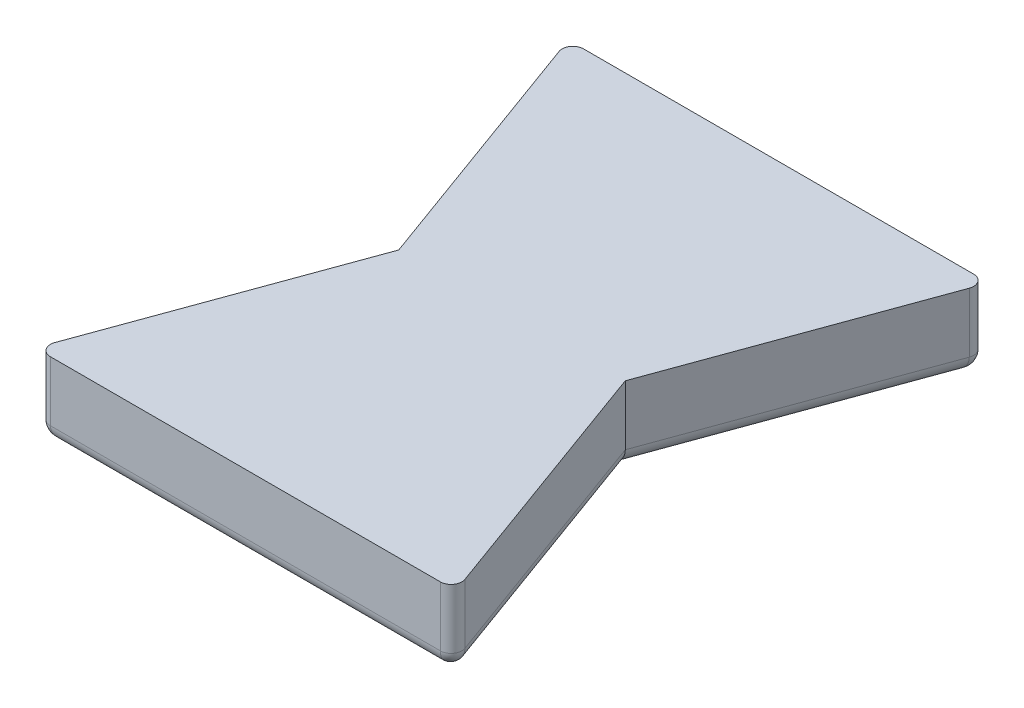
SolidWorks part; units mm, degrees
ref_plane "Front Plane" through (0, 0, 0) normal (0, 0, 1) x (1, 0, 0)
ref_plane "Top Plane" through (0, 0, 0) normal (0, 1, 0) x (1, 0, 0)
ref_plane "Right Plane" through (0, 0, 0) normal (1, 0, 0) x (0, 0, -1)
sketch "Sketch1" plane through (0, 0, 0) normal (0, 1, 0) x (1, 0, 0)
  line L0 (-13.0563, 17.5) -> (14.6826, 17.5) construction
  line L1 (14.6826, 17.5) -> (8.3132, 0) construction
  line L2 (8.3132, 0) -> (14.6826, -17.5) construction
  line L3 (14.6826, -17.5) -> (-13.0563, -17.5) construction
  line L4 (-13.0563, -17.5) -> (-6.6868, 0) construction
  line L5 (-6.6868, 0) -> (-13.0563, 17.5) construction
  line L6 (-6.6868, 0) -> (8.3132, 0) construction
  line L7 (14.5398, -17.4) -> (-12.9135, -17.4)
  line L8 (-12.9135, -17.4) -> (-6.5804, 0)
  line L9 (-6.5804, 0) -> (-12.9135, 17.4)
  line L10 (-12.9135, 17.4) -> (14.5398, 17.4)
  line L11 (14.5398, 17.4) -> (8.2067, 0)
  line L12 (8.2067, 0) -> (14.5398, -17.4)
  dimension "D1" = 15
  dimension "D2" = 35
  dimension "D3" = 70
  dimension "D4" = 0.1
extrude "Boss-Extrude1" add sketch "Sketch1" along normal blind 4.9
fillet "Fillet1" radius 0.7 4 edges at (14.5398, 2.45, -17.4) (-12.9135, 2.45, -17.4) (-12.9135, 2.45, 17.4) (14.5398, 2.45, 17.4)
fillet "Fillet2" radius 1 10 edges at (-12.4872, 0, -17.1015) (-9.576, 0, -8.2303) (-9.576, 0, 8.2303) (-12.4872, 0, 17.1015) (0.8132, 0, 17.4) (14.1135, 0, 17.1015) (11.2023, 0, 8.2303) (11.2023, 0, -8.2303) (14.1135, 0, -17.1015) (0.8132, 0, -17.4)
